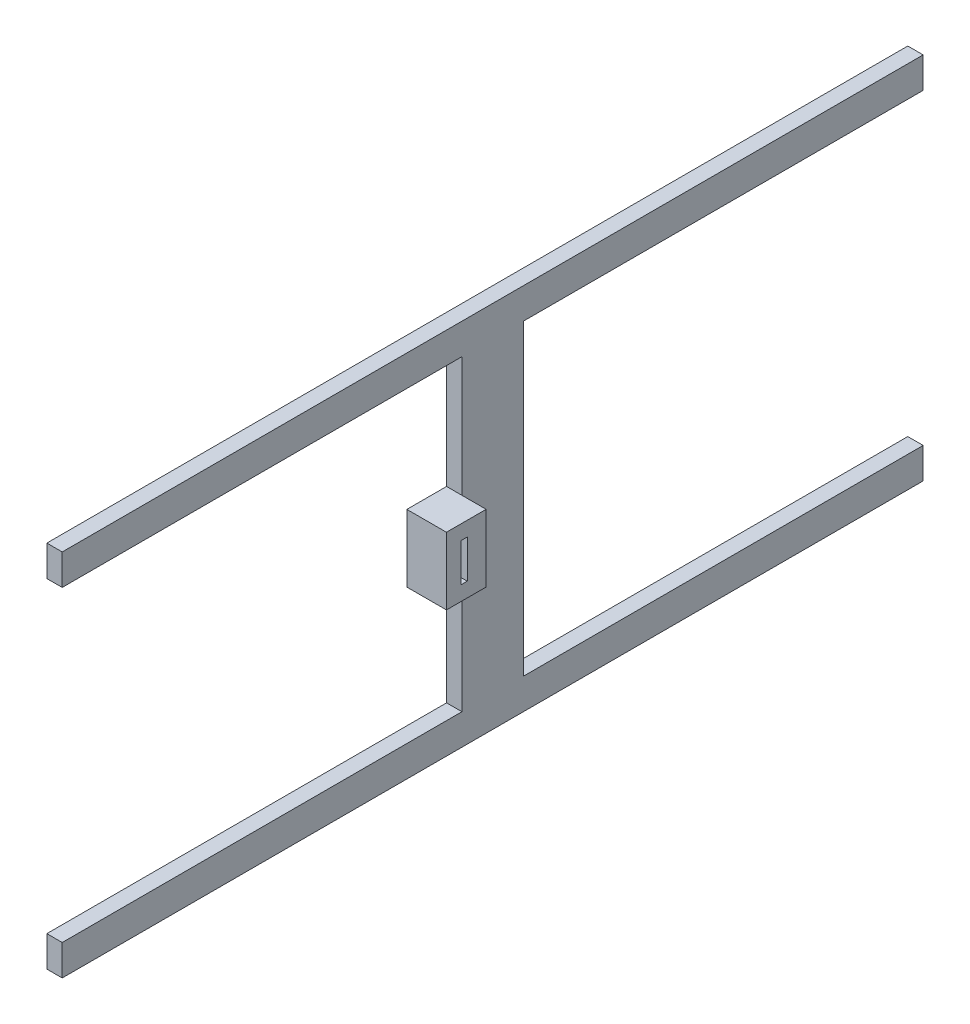
SolidWorks part; units mm, degrees
ref_plane "Front" through (0, 0, 0) normal (0, 0, 1) x (1, 0, 0)
ref_plane "Top" through (0, 0, 0) normal (0, 1, 0) x (1, 0, 0)
ref_plane "Right" through (0, 0, 0) normal (1, 0, 0) x (0, 0, -1)
sketch "Sketch1" plane through (0, 0, 0) normal (1, 0, 0) x (0, 0, -1)
  line L0 (0, 0) -> (32.4322, 0)
  line L1 (32.4322, 31.75) -> (32.4322, -31.75)
  line L2 (32.4322, -31.75) -> (114.9822, -31.75)
  line L3 (114.9822, -31.75) -> (114.9822, -38.1)
  line L4 (114.9822, -38.1) -> (-62.8178, -38.1)
  line L5 (-62.8178, -38.1) -> (-62.8178, -31.75)
  line L6 (-62.8178, -31.75) -> (19.7322, -31.75)
  line L7 (19.7322, -31.75) -> (19.7322, 31.75)
  line L8 (19.7322, 0) -> (0, 0)
  line L9 (-62.8178, 31.75) -> (19.7322, 31.75)
  line L10 (-62.8178, 38.1) -> (-62.8178, 31.75)
  line L11 (114.9822, 38.1) -> (-62.8178, 38.1)
  line L12 (114.9822, 31.75) -> (114.9822, 38.1)
  line L13 (32.4322, 31.75) -> (114.9822, 31.75)
  point P10 (-62.8178, -34.925)
  dimension "D1" = 177.8
  dimension "D2" = 12.7
  dimension "D3" = 82.55
  dimension "D4" = 31.75
  dimension "D5" = 6.35
extrude "Boss-Extrude1" add sketch "Sketch1" along normal blind 3.175 contours L1 L13 L12 L11 L10 L9 L7 L0 | L7 L6 L5 L4 L3 L2 L1 L0 region at (0, 29.9118, -26.0822) region at (0, -29.9118, -26.0822)
sketch "Sketch2" plane through (0, 0, 0) normal (-1, 0, 0) x (0, 0, 1)
  line L0 (-19.7322, 3.95) -> (-14.5322, 3.95)
  line L1 (-19.7322, -31.75) -> (-19.7322, 31.75) construction
  line L2 (-14.5322, 3.95) -> (-14.5322, -3.95)
  line L3 (-14.5322, -3.95) -> (-19.7322, -3.95)
  line L4 (-19.7322, -31.75) -> (-19.7322, -3.95)
  line L5 (-19.7322, 3.95) -> (-19.7322, 6.95)
  line L6 (-19.7322, 6.95) -> (-11.5322, 6.95)
  line L7 (-11.5322, 6.95) -> (-11.5322, -6.95)
  line L8 (-11.5322, -6.95) -> (-19.7322, -6.95)
  line L16 (-32.4322, 31.75) -> (-32.4322, -31.75)
  line L17 (-32.4322, -31.75) -> (-114.9822, -31.75)
  line L18 (-114.9822, -31.75) -> (-114.9822, -38.1)
  line L19 (-114.9822, -38.1) -> (62.8178, -38.1)
  line L20 (62.8178, -38.1) -> (62.8178, -31.75)
  line L21 (62.8178, -31.75) -> (-19.7322, -31.75)
  line L22 (-19.7322, -31.75) -> (-19.7322, 31.75)
  line L23 (-19.7322, 31.75) -> (62.8178, 31.75)
  line L24 (62.8178, 31.75) -> (62.8178, 38.1)
  line L25 (62.8178, 38.1) -> (-114.9822, 38.1)
  line L26 (-114.9822, 38.1) -> (-114.9822, 31.75)
  line L27 (-114.9822, 31.75) -> (-32.4322, 31.75)
  line L28 (-32.4322, 31.75) -> (-32.4322, -31.75)
  line L29 (-32.4322, -31.75) -> (-114.9822, -31.75)
  line L30 (-114.9822, -31.75) -> (-114.9822, -38.1)
  line L31 (-114.9822, -38.1) -> (62.8178, -38.1)
  line L32 (62.8178, -38.1) -> (62.8178, -31.75)
  line L33 (62.8178, -31.75) -> (-19.7322, -31.75)
  line L34 (-19.7322, 3.95) -> (-19.7322, 31.75)
  line L35 (-19.7322, 31.75) -> (62.8178, 31.75)
  line L36 (62.8178, 31.75) -> (62.8178, 38.1)
  line L37 (62.8178, 38.1) -> (-114.9822, 38.1)
  line L38 (-114.9822, 38.1) -> (-114.9822, 31.75)
  line L39 (-114.9822, 31.75) -> (-32.4322, 31.75)
  point P16 (-14.5322, 0)
  point P18 (-19.7322, 0)
  line M25 (-19.7322, -31.75) -> (-19.7322, 31.75)
  dimension "D2" = 7.9
  dimension "D3" = 5.2
  dimension "D4" = 3
  dimension "D5" = 3
  dimension "D6" = 0
  dimension "D7" = 3
  dimension "D1" = 0
extrude "Boss-Extrude2" add sketch "Sketch2" against normal blind 5 contours L8 L7 L6 L0 L2 L3 L4 M25 region at (0, 5.45, -19.5708)
sketch "Sketch4" plane through (5, 0, 0) normal (1, 0, 0) x (0, 0, -1)
  line L0 (19.7322, 6.95) -> (11.5322, 6.95)
  line L1 (11.5322, 6.95) -> (11.5322, -6.95)
  line L2 (11.5322, -6.95) -> (19.7322, -6.95)
  line L3 (19.7322, -6.95) -> (19.7322, -3.95)
  line L4 (19.7322, -3.95) -> (15.8322, -3.95)
  line L5 (14.5322, -3.95) -> (19.7322, -3.95) construction
  line L6 (15.8322, -3.95) -> (15.8322, 3.95)
  line L7 (19.7322, 3.95) -> (14.5322, 3.95) construction
  line L8 (15.8322, 3.95) -> (19.7322, 3.95)
  line L9 (19.7322, 3.95) -> (19.7322, 6.95)
  line L10 (19.7322, 3.95) -> (19.7322, -3.95)
  line L11 (15.8322, 3.95) -> (14.5322, 3.95)
  line L12 (14.5322, 3.95) -> (14.5322, -3.95)
  line L13 (14.5322, -3.95) -> (15.8322, -3.95)
  line M1 (11.5322, -6.95) -> (19.7322, -6.95)
  line M2 (19.7322, -6.95) -> (19.7322, -3.95)
  line M3 (19.7322, -3.95) -> (14.5322, -3.95)
  line M4 (14.5322, -3.95) -> (14.5322, 3.95)
  line M5 (14.5322, 3.95) -> (19.7322, 3.95)
  line M6 (19.7322, 3.95) -> (19.7322, 6.95)
  line M7 (19.7322, 6.95) -> (11.5322, 6.95)
  line M8 (11.5322, 6.95) -> (11.5322, -6.95)
  dimension "D1" = 1.3
extrude "Boss-Extrude3" add sketch "Sketch4" along normal blind 3.175 contours M8 M1 M2 M3 M4 M5 M6 M7 | L10 L6 M5 M3 region at (5, 5.45, -19.5708) region at (5, 0, -17.7822)
